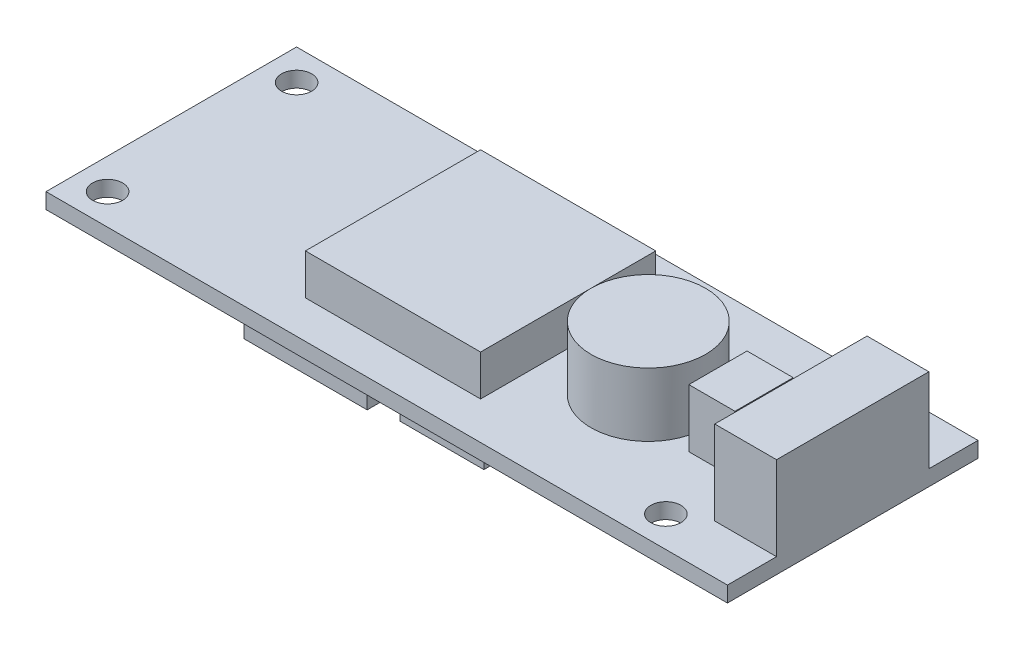
SolidWorks part; units mm, degrees
ref_plane "Front Plane" through (0, 0, 0) normal (0, 0, 1) x (1, 0, 0)
ref_plane "Top Plane" through (0, 0, 0) normal (0, 1, 0) x (1, 0, 0)
ref_plane "Right Plane" through (0, 0, 0) normal (1, 0, 0) x (0, 0, -1)
sketch "Sketch1" plane through (0, 0, 0) normal (0, 1, 0) x (1, 0, 0)
  line L0 (27.065, 12.8714) -> (27.065, -12.8715) construction
  line L1 (-35.0025, -12.8715) -> (35.0025, -12.8715)
  line L2 (-35.0025, -12.8715) -> (-35.0025, 12.8714)
  line L3 (-35.0025, 12.8714) -> (35.0025, 12.8714)
  line L4 (35.0025, -12.8715) -> (35.0025, 12.8714)
  line L5 (-35.0025, -12.8715) -> (35.0025, 12.8714) construction
  line L6 (-35.0025, 12.8714) -> (35.0025, -12.8715) construction
  line L7 (31.8402, -9.7091) -> (-31.8402, -9.7091) construction
  line L8 (31.8402, -9.7091) -> (31.8402, 9.7092) construction
  line L9 (31.8402, 9.7092) -> (-31.8402, 9.7092) construction
  line L10 (-31.8402, -9.7091) -> (-31.8402, 9.7092) construction
  line L11 (31.8402, -9.7091) -> (-31.8402, 9.7092) construction
  line L12 (31.8402, 9.7092) -> (-31.8402, -9.7091) construction
  line L13 (0, -11.2585) -> (-33.3896, -11.2586) construction
  line L14 (0, -11.2585) -> (0, 11.2585) construction
  line L15 (0, 11.2585) -> (-33.3896, 11.2585) construction
  line L16 (-33.3896, -11.2586) -> (-33.3896, 11.2585) construction
  circle A0 centre (-31.8402, 9.7092) radius 1.5494
  circle A1 centre (-31.8402, -9.7091) radius 1.5494
  circle A4 centre (25.5156, 9.7092) radius 1.5494
  circle A5 centre (25.5156, -9.7091) radius 1.5494
  point P0 (0, 0)
  point P6 (0, 0)
  point P15 (0, 0)
  point P24 (0, 0)
  point P25 (0, 0)
  dimension "D5" = 3.0988
  dimension "D1" = 25.7429
  dimension "D2" = 70.0049
  dimension "D3" = 1.6129
  dimension "D4" = 1.6129
  dimension "D6" = 7.9375
extrude "PCB" add sketch "Sketch1" along normal blind 1.6002
sketch "top_features" plane through (0, 1.6002, 0) normal (0, 1, 0) x (1, 0, 0)
  line L0 (-35.0025, 0) -> (35.0025, 0) construction
  line L1 (28.6499, 7.8245) -> (35.0025, 7.8245)
  line L2 (28.6499, 7.8245) -> (28.6499, -7.8245)
  line L3 (28.6499, -7.8245) -> (35.0025, -7.8245)
  line L4 (35.0025, 7.8245) -> (35.0025, -7.8245)
  line L5 (21.1569, 2.9908) -> (25.8969, 2.9908)
  line L6 (21.1569, 2.9908) -> (21.1569, -2.9908)
  line L7 (21.1569, -2.9908) -> (25.8969, -2.9908)
  line L8 (25.8969, 2.9908) -> (25.8969, -2.9908)
  line L9 (-12.2263, 8.9979) -> (5.7696, 8.9979)
  line L10 (-12.2263, 8.9979) -> (-12.2263, -8.9979)
  line L11 (-12.2263, -8.9979) -> (5.7696, -8.9979)
  line L12 (5.7696, 8.9979) -> (5.7696, -8.9979)
  line L13 (-35.0025, 12.8714) -> (-35.0025, -12.8715) construction
  line L14 (35.0025, -12.8715) -> (35.0025, 12.8714) construction
  line L16 (8.1175, 0) -> (8.1175, 50000) construction
  circle A0 centre (14.0025, 0) radius 5.885
  point P18 (35.0025, 0)
  point P19 (25.8969, 0)
  point P20 (5.7696, 0)
  dimension "D9" = 11.77
  dimension "D1" = 5.9817
  dimension "D2" = 15.6489
  dimension "D3" = 17.9959
  dimension "D4" = 17.9959
  dimension "D5" = 4.74
  dimension "D6" = 22.7762
  dimension "D7" = 56.1594
  dimension "D8" = 6.3525
  dimension "D10" = 43.12
sketch "bottom_features" plane through (0, 0, 0) normal (0, -1, 0) x (1, 0, 0)
  line L0 (35.0025, -12.8714) -> (-35.0025, -12.8714) construction
  line L1 (-21.2025, 0.3124) -> (-16.1987, 0.3124)
  line L2 (-21.2025, 0.3124) -> (-21.2025, -4.6914)
  line L3 (-21.2025, -4.6914) -> (-16.1987, -4.6914)
  line L4 (-16.1987, 0.3124) -> (-16.1987, -4.6914)
  line L5 (-15.8425, 11.7115) -> (-3.1679, 11.7115)
  line L6 (-15.8425, 11.7115) -> (-15.8425, 1.1197)
  line L7 (-15.8425, 1.1197) -> (-3.1679, 1.1197)
  line L8 (-3.1679, 11.7115) -> (-3.1679, 1.1197)
  line L9 (-14.0491, -5.9242) -> (-9.0225, -5.9242)
  line L10 (-14.0491, -5.9242) -> (-14.0491, -8.9214)
  line L11 (-14.0491, -8.9214) -> (-9.0225, -8.9214)
  line L12 (-9.0225, -5.9242) -> (-9.0225, -8.9214)
  line L13 (0.5065, 12.0315) -> (9.1425, 12.0315)
  line L14 (0.5065, 12.0315) -> (0.5065, 6.761)
  line L15 (0.5065, 6.761) -> (9.1425, 6.761)
  line L16 (9.1425, 12.0315) -> (9.1425, 6.761)
  line L17 (2.2702, 2.7509) -> (9.2425, 2.7509)
  line L18 (2.2702, 2.7509) -> (2.2702, -4.2214)
  line L19 (2.2702, -4.2214) -> (9.2425, -4.2214)
  line L20 (9.2425, 2.7509) -> (9.2425, -4.2214)
  line L21 (11.4534, -7.0421) -> (19.4925, -7.0421)
  line L22 (11.4534, -7.0421) -> (11.4534, -12.8714)
  line L23 (11.4534, -12.8714) -> (19.4925, -12.8714)
  line L24 (19.4925, -7.0421) -> (19.4925, -12.8714)
  line L25 (-35.0025, -12.8714) -> (-35.0025, 12.8715) construction
  line L26 (-35.0025, 12.8715) -> (35.0025, 12.8715) construction
  line L27 (35.0025, 12.8715) -> (35.0025, -12.8714) construction
  line L28 (35.0025, -7.8245) -> (35.0025, 7.8245) construction
  line L29 (31.3925, 6.4) -> (31.3925, -6.4) construction
  line L30 (11.2525, 9.5315) -> (16.2925, 9.5315)
  line L31 (11.2525, 9.5315) -> (11.2525, 6.5115)
  line L32 (11.2525, 6.5115) -> (16.2925, 6.5115)
  line L33 (16.2925, 9.5315) -> (16.2925, 6.5115)
  line L34 (32.2525, 6.4) -> (32.2525, -6.4)
  line L35 (30.5325, 6.4) -> (30.5325, -6.4)
  line L36 (32.0875, 7.26) -> (50032.0875, 7.26) construction
  line L37 (32.0875, -7.26) -> (50032.0875, -7.26) construction
  line L39 (-35.0025, 0) -> (35.0025, 0) construction
  line L41 (25.8425, 1.8385) -> (29.0925, 1.8385)
  line L42 (25.8425, 1.8385) -> (25.8425, 0.1685)
  line L43 (25.8425, 0.1685) -> (29.0925, 0.1685)
  line L44 (29.0925, 1.8385) -> (29.0925, 0.1685)
  arc A0 (32.2525, 6.4) -> (30.5325, 6.4) centre (31.3925, 6.4) ccw
  arc A1 (30.5325, -6.4) -> (32.2525, -6.4) centre (31.3925, -6.4) ccw
  point P40 (31.3925, 0)
  point P47 (31.3925, 7.26)
  point P50 (31.3925, -7.26)
  dimension "D1" = 5.0038
  dimension "D2" = 10.5918
  dimension "D3" = 12.6746
  dimension "D4" = 5.0267
  dimension "D5" = 2.9972
  dimension "D6" = 5.2705
  dimension "D7" = 8.636
  dimension "D8" = 8.0391
  dimension "D9" = 5.8293
  dimension "D10" = 6.9723
  dimension "D11" = 8.18
  dimension "D12" = 13.8
  dimension "D13" = 19.16
  dimension "D14" = 1.16
  dimension "D15" = 0.84
  dimension "D16" = 25.86
  dimension "D17" = 8.65
  dimension "D18" = 25.76
  dimension "D19" = 15.51
  dimension "D20" = 25.98
  dimension "D21" = 3.95
  dimension "D22" = 5.04
  dimension "D23" = 3.02
  dimension "D24" = 3.34
  dimension "D25" = 18.71
  dimension "D26" = 1.72
  dimension "D27" = 14.52
  dimension "D28" = 2.75
  dimension "D29" = 1.67
  dimension "D30" = 3.25
  dimension "D31" = 5.91
  dimension "D32" = 13.04
extrude "gps_antenna" add sketch "top_features" along normal blind 4.18 contours L9 L12 L11 L10
extrude "jst_connector" add sketch "Sketch2<3>" along normal blind 5.97 contours L7 L8 L5 L6
sketch "Sketch2<3>" plane through (0, 1.6002, 0) normal (0, 1, 0) x (1, 0, 0) same geometry as "top_features"
extrude "terminal_block" add sketch "Sketch2<4>" along normal blind 8.63 contours L3 L4 L1 L2
sketch "Sketch2<4>" plane through (0, 1.6002, 0) normal (0, 1, 0) x (1, 0, 0) same geometry as "top_features"
extrude "cc1200" add sketch "bottom_features" along normal blind 1.13 contours L2 L3 L4 L1
extrude "ublox" add sketch "bottom_features<4>" along normal blind 2.48 contours L6 L7 L8 L5
sketch "bottom_features<4>" plane through (0, 0, 0) normal (0, -1, 0) x (1, 0, 0) same geometry as "bottom_features"
extrude "flash" add sketch "bottom_features<5>" along normal blind 1.48 contours L14 L15 L16 L13
sketch "bottom_features<5>" plane through (0, 0, 0) normal (0, -1, 0) x (1, 0, 0) same geometry as "bottom_features"
extrude "baro" add sketch "bottom_features<6>" along normal blind 1.22 contours L32 L33 L30 L31
sketch "bottom_features<6>" plane through (0, 0, 0) normal (0, -1, 0) x (1, 0, 0) same geometry as "bottom_features"
extrude "uC" add sketch "bottom_features<7>" along normal blind 0.87 contours L20 L19 L18 L17
sketch "bottom_features<7>" plane through (0, 0, 0) normal (0, -1, 0) x (1, 0, 0) same geometry as "bottom_features"
extrude "usb" add sketch "bottom_features<8>" along normal blind 2.57 contours L22 L23 L24 L21
sketch "bottom_features<8>" plane through (0, 0, 0) normal (0, -1, 0) x (1, 0, 0) same geometry as "bottom_features"
extrude "accelerometer" add sketch "bottom_features<9>" along normal blind 1.12 contours L11 L12 L9 L10
sketch "bottom_features<9>" plane through (0, 0, 0) normal (0, -1, 0) x (1, 0, 0) same geometry as "bottom_features"
extrude "terminalblock_solder" add sketch "bottom_features<10>" along normal blind 2.17 contours L34 A1 L35 A0
sketch "bottom_features<10>" plane through (0, 0, 0) normal (0, -1, 0) x (1, 0, 0) same geometry as "bottom_features"
extrude "Boss-Extrude13" add sketch "top_features<5>" along normal blind 6.53 contours A0 region at (14.0025, 1.6002, 0)
sketch "top_features<5>" plane through (0, 1.6002, 0) normal (0, 1, 0) x (1, 0, 0) same geometry as "top_features"
